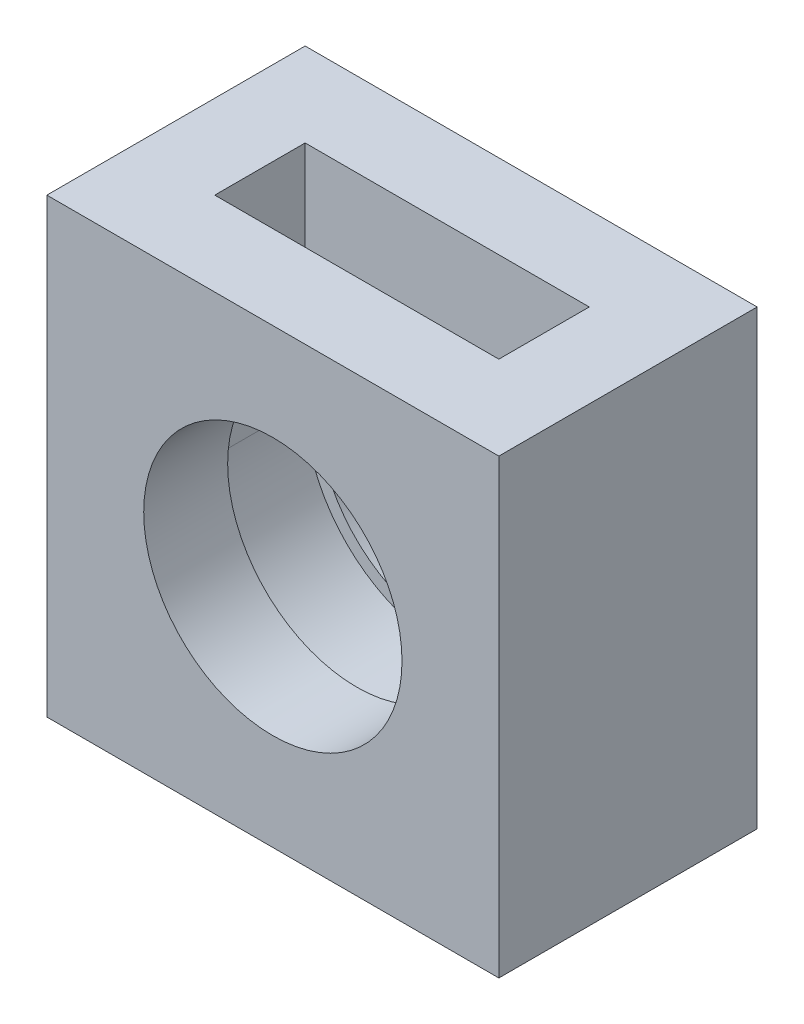
SolidWorks part; units mm, degrees
ref_plane "Front Plane" through (0, 0, 0) normal (0, 0, 1) x (1, 0, 0)
ref_plane "Top Plane" through (0, 0, 0) normal (0, 1, 0) x (1, 0, 0)
ref_plane "Right Plane" through (0, 0, 0) normal (1, 0, 0) x (0, 0, -1)
sketch "Sketch2" plane through (0, 0, 0) normal (0, 0, 1) x (1, 0, 0)
  line L1 (-17.5, -17.5) -> (17.5, -17.5)
  line L2 (-17.5, -17.5) -> (-17.5, 17.5)
  line L3 (-17.5, 17.5) -> (17.5, 17.5)
  line L4 (17.5, -17.5) -> (17.5, 17.5)
  line L5 (-17.5, -17.5) -> (17.5, 17.5) construction
  line L6 (-17.5, 17.5) -> (17.5, -17.5) construction
  circle A0 centre (0, 0) radius 10
  dimension "D1" = 20
  dimension "D2" = 35
  dimension "D3" = 35
extrude "Boss-Extrude1" add sketch "Sketch2" along normal blind 20
sketch "Sketch3" plane through (0, 0, 0) normal (0, 0, 1) x (1, 0, 0)
  line L0 (-11, 17.5) -> (-11, 0)
  line L1 (17.5, 17.5) -> (-17.5, 17.5) construction
  line L2 (11, 17.5) -> (11, 0)
  line L3 (0, 0) -> (0, 17.5) construction
  line L9 (11, 17.5) -> (-11, 17.5)
  arc A0 (11, 0) -> (-11, 0) centre (0, 0) cw
  point P10 (0, -0.3687)
  dimension "D2" = 22
ref_plane "Plane1" through (0, 0, 10) normal (0, 0, -1) x (-1, 0, 0)
extrude "Cut-Extrude2" cut sketch "Sketch3" along normal mid plane 7 from surface starting at plane "Plane1"
